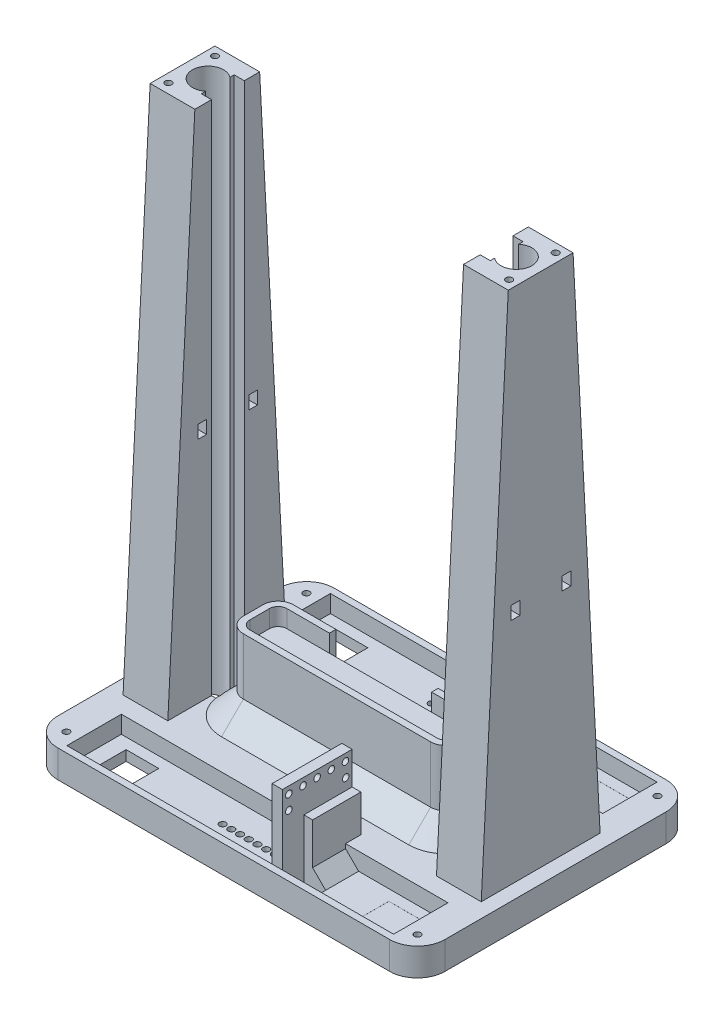
SolidWorks part; units mm, degrees
ref_plane "Front Plane" through (0, 0, 0) normal (0, 0, 1) x (1, 0, 0)
ref_plane "Top Plane" through (0, 0, 0) normal (0, 1, 0) x (1, 0, 0)
ref_plane "Right Plane" through (0, 0, 0) normal (1, 0, 0) x (0, 0, -1)
sketch "Sketch1" plane through (0, 0, 0) normal (0, 1, 0) x (1, 0, 0)
  line L1 (-76.2, 63.5) -> (76.2, 63.5)
  line L2 (-88.9, 50.8) -> (-88.9, -50.8)
  line L3 (-76.2, -63.5) -> (76.2, -63.5)
  line L4 (88.9, 50.8) -> (88.9, -50.8)
  line L5 (-88.9, 63.5) -> (88.9, -63.5) construction
  line L6 (-88.9, -63.5) -> (88.9, 63.5) construction
  arc A0 (-88.9, -50.8) -> (-76.2, -63.5) centre (-76.2, -50.8) ccw
  arc A1 (76.2, -63.5) -> (88.9, -50.8) centre (76.2, -50.8) ccw
  arc A2 (76.2, 63.5) -> (88.9, 50.8) centre (76.2, 50.8) cw
  arc A3 (-76.2, 63.5) -> (-88.9, 50.8) centre (-76.2, 50.8) ccw
  point P0 (0, 0)
  dimension "D3" = 12.7
  dimension "D1" = 177.8
  dimension "D2" = 127
extrude "Boss-Extrude1" add sketch "Sketch1" along normal blind 12.7
sketch "Sketch4" plane through (0, 12.7, 0) normal (0, 1, 0) x (1, 0, 0)
  line L5 (45, -6.5) -> (-45, -6.5)
  line L6 (45, -6.5) -> (45, 6.5)
  line L7 (45, 6.5) -> (-45, 6.5)
  line L8 (-45, -6.5) -> (-45, 6.5)
  line L9 (45, -6.5) -> (-45, 6.5) construction
  line L10 (45, 6.5) -> (-45, -6.5) construction
  point P0 (0, 0)
  dimension "D1" = 13
  dimension "D2" = 90
extrude "Cut-Extrude3" cut sketch "Sketch4" against normal blind 8
sketch "Sketch5" plane through (0, 12.7, 0) normal (0, 1, 0) x (1, 0, 0)
  line L0 (45, 6.5) -> (-45, 6.5) construction
  line L1 (-16.4675, 6.5) -> (-21.4675, 6.5)
  line L2 (-16.4675, 6.5) -> (-16.4675, 56.5)
  line L3 (-16.4675, 56.5) -> (-21.4675, 56.5)
  line L4 (-21.4675, 6.5) -> (-21.4675, 56.5)
  line L5 (0, -6.985) -> (0, 6.985) construction
  line L6 (16.4675, 56.5) -> (21.4675, 56.5)
  line L7 (21.4675, 6.5) -> (21.4675, 56.5)
  line L8 (16.4675, 6.5) -> (21.4675, 6.5)
  line L9 (16.4675, 6.5) -> (16.4675, 56.5)
  dimension "D1" = 5
  dimension "D2" = 50
  dimension "D3" = 16.4675
extrude "Cut-Extrude4" cut sketch "Sketch5" against normal up to surface (8 mm away) up to face at (0, 4.7, 0)
fillet "Fillet2" radius 2 36 edges at (21.4675, 4.7, -31.5) (21.4675, 12.7, -31.5) (16.4675, 4.7, -31.5) (16.4675, 12.7, -31.5) (-16.4675, 4.7, -31.5) (-16.4675, 12.7, -31.5) (-21.4675, 4.7, -31.5) (-21.4675, 12.7, -31.5) (-45, 4.7, 0) (-45, 12.7, 0) (-45, 8.7, 6.5) (0, 4.7, 6.5) (0, 12.7, 6.5) (45, 8.7, 6.5) (45, 4.7, 0) (45, 12.7, 0) (45, 8.7, -6.5) (33.2338, 4.7, -6.5) (21.4675, 8.7, -6.5) (33.2338, 12.7, -6.5) (16.4675, 8.7, -6.5) (0, 4.7, -6.5) (-16.4675, 8.7, -6.5) (0, 12.7, -6.5) (-45, 8.7, -6.5) (-33.2338, 12.7, -6.5) (-21.4675, 8.7, -6.5) (-33.2338, 4.7, -6.5) (-21.4675, 8.7, -56.5) (-18.9675, 12.7, -56.5) (-16.4675, 8.7, -56.5) (-18.9675, 4.7, -56.5) (16.4675, 8.7, -56.5) (18.9675, 12.7, -56.5) (21.4675, 8.7, -56.5) (18.9675, 4.7, -56.5)
sketch "Sketch8" plane through (0, 12.7, 0) normal (0, 1, 0) x (1, 0, 0)
  line L0 (-76.2, -63.5) -> (76.2, -63.5) construction
  line L1 (-75, -35.5) -> (75, -35.5)
  line L2 (-75, -35.5) -> (-75, -60.5)
  line L3 (-75, -60.5) -> (75, -60.5)
  line L4 (75, -35.5) -> (75, -60.5)
  line L5 (-6.985, 0) -> (6.985, 0) construction
  line L6 (-75, 60.5) -> (75, 60.5)
  line L7 (75, 35.5) -> (75, 60.5)
  line L8 (-75, 35.5) -> (75, 35.5)
  line L9 (-75, 35.5) -> (-75, 60.5)
  point P4 (0, -60.5)
  dimension "D1" = 25
  dimension "D2" = 150
  dimension "D3" = 3
extrude "Cut-Extrude7" cut sketch "Sketch8" against normal blind 8
sketch "Sketch9" plane through (0, 4.7, 0) normal (0, 1, 0) x (1, 0, 0)
  line L0 (-75, -35.5) -> (-75, -60.5) construction
  line L1 (0, -6.985) -> (0, 6.985) construction
  line L2 (-6.985, 0) -> (6.985, 0) construction
  circle A0 centre (0, -48) radius 1.5
  circle A1 centre (4, -48) radius 1.5
  circle A2 centre (8, -48) radius 1.5
  circle A3 centre (12, -48) radius 1.5
  circle A4 centre (16, -48) radius 1.5
  circle A5 centre (-16, -48) radius 1.5
  circle A6 centre (-12, -48) radius 1.5
  circle A7 centre (-8, -48) radius 1.5
  circle A8 centre (-4, -48) radius 1.5
  circle A9 centre (-4, 48) radius 1.5
  circle A10 centre (-8, 48) radius 1.5
  circle A11 centre (-12, 48) radius 1.5
  circle A12 centre (-16, 48) radius 1.5
  circle A13 centre (16, 48) radius 1.5
  circle A14 centre (12, 48) radius 1.5
  circle A15 centre (8, 48) radius 1.5
  circle A16 centre (4, 48) radius 1.5
  circle A17 centre (0, 48) radius 1.5
  point P7 (-75, -48)
  dimension "D1" = 3
  dimension "D2" = 5
extrude "Cut-Extrude8" cut sketch "Sketch9" against normal blind 8
sketch "Sketch10" plane through (0, 4.7, 0) normal (0, 1, 0) x (1, 0, 0)
  line L0 (-75, -35.5) -> (-75, -60.5) construction
  line L1 (-67.8176, -40.5) -> (-52.8176, -40.5)
  line L2 (-67.8176, -40.5) -> (-67.8176, -55.5)
  line L3 (-67.8176, -55.5) -> (-52.8176, -55.5)
  line L4 (-52.8176, -40.5) -> (-52.8176, -55.5)
  line L5 (0, -6.985) -> (0, 6.985) construction
  line L6 (52.8176, -40.5) -> (52.8176, -55.5)
  line L7 (67.8176, -40.5) -> (52.8176, -40.5)
  line L8 (67.8176, -55.5) -> (52.8176, -55.5)
  line L9 (67.8176, -40.5) -> (67.8176, -55.5)
  line L10 (-6.985, 0) -> (6.985, 0) construction
  line L11 (-75, 35.5) -> (-75, 60.5) construction
  line L12 (67.8176, 40.5) -> (67.8176, 55.5)
  line L13 (67.8176, 55.5) -> (52.8176, 55.5)
  line L14 (67.8176, 40.5) -> (52.8176, 40.5)
  line L15 (52.8176, 40.5) -> (52.8176, 55.5)
  line L16 (-52.8176, 40.5) -> (-52.8176, 55.5)
  line L17 (-67.8176, 55.5) -> (-52.8176, 55.5)
  line L18 (-67.8176, 40.5) -> (-67.8176, 55.5)
  line L19 (-67.8176, 40.5) -> (-52.8176, 40.5)
  point P8 (-67.8176, -48)
  point P9 (-75, -48)
  dimension "D1" = 15
extrude "Cut-Extrude9" cut sketch "Sketch10" against normal blind 8
sketch "Sketch11" plane through (0, 4.7, 0) normal (0, 1, 0) x (1, 0, 0)
  circle A0 centre (-19.4973, 37.2145) radius 2
  circle A1 centre (18.951, 37.4322) radius 2
  dimension "D1" = 4
  dimension "D2" = 4
extrude "Cut-Extrude10" cut sketch "Sketch11" against normal through all both and the other way through all
sketch "Sketch13" plane through (0, 12.7, 0) normal (0, 1, 0) x (1, 0, 0)
  line L1 (-82.2291, 27.1098) -> (-57.5332, 27.1098)
  line L2 (-82.2291, 27.1098) -> (-82.2291, -27.4812)
  line L3 (-82.2291, -27.4812) -> (-57.5332, -27.4812)
  line L4 (-57.5332, 27.1098) -> (-57.5332, -27.4812)
extrude "Boss-Extrude2" add sketch "Sketch13" along normal blind 242
sketch "Sketch14" plane through (-88.9, 0, 0) normal (-1, 0, 0) x (0, 0, 1)
  line L0 (-50.8, 12.7) -> (-50.8, 0)
  line L1 (-63.5, 0) -> (-50.8, 0) construction
  dimension "D1" = 12.7
sketch "Sketch17" plane through (-82.2291, 0, 0) normal (-1, 0, 0) x (0, 0, 1)
  line L0 (-27.1098, 12.7) -> (-14.6891, 249.7)
  line L1 (-27.1098, 254.7) -> (27.4812, 254.7) construction
  line L2 (-14.4271, 254.7) -> (14.7985, 254.7)
  line L3 (15.0605, 249.7) -> (27.4812, 12.7)
  line L4 (-50.8, 12.7) -> (50.8, 12.7) construction
  line L5 (27.4812, 254.7) -> (27.4812, 12.7) construction
  line L6 (27.4812, 12.7) -> (27.4812, 254.7)
  line L7 (27.4812, 254.7) -> (-27.1098, 254.7)
  line L8 (-27.1098, 254.7) -> (-27.1098, 12.7)
  line L9 (-14.6891, 249.7) -> (15.0605, 249.7)
  line L10 (27.4812, 249.7) -> (27.4812, 254.7)
  line L11 (-27.1098, 254.7) -> (-27.1098, 249.7)
  line L12 (-27.1098, 254.7) -> (27.4812, 254.7)
  line L13 (-27.1098, 12.7) -> (27.4812, 12.7) construction
  line L15 (-27.1098, 254.7) -> (27.4812, 254.7)
  line L16 (-27.1098, 254.7) -> (-27.1098, 249.7)
  line L17 (-14.6891, 249.7) -> (15.0605, 249.7)
  line L18 (27.4812, 254.7) -> (27.4812, 249.7)
  line M6 (27.4812, 12.7) -> (27.4812, 254.7)
  line M7 (27.4812, 254.7) -> (-27.1098, 254.7)
  line M8 (-27.1098, 254.7) -> (-27.1098, 12.7)
  dimension "D1" = 93
  dimension "D2" = 93
  dimension "D3" = 237
extrude "Cut-Extrude11" cut sketch "Sketch17" against normal through all both and the other way through all contours L0 M8 M7 | L3 M7 M6
mirror "Mirror1" about plane through (0, 0, 0) normal (1, 0, 0) of "Cut-Extrude11", "Boss-Extrude2"
sketch "Sketch19" plane through (0, 249.7, 0) normal (0, 1, 0) x (1, 0, 0)
  line L0 (-57.5332, 14.6891) -> (57.5332, 14.6891) construction
  dimension "D1" = 115.0664
sketch "Sketch21" plane through (57.5332, 0, 0) normal (-1, 0, 0) x (0, 0, 1)
  line L0 (27.4812, 12.7) -> (-27.1098, 12.7) construction
  line L1 (9.7062, 123.7) -> (13.7062, 123.7)
  line L2 (9.7062, 123.7) -> (9.7062, 117.7)
  line L3 (9.7062, 117.7) -> (13.7062, 117.7)
  line L4 (13.7062, 123.7) -> (13.7062, 117.7)
  line L5 (7.0117, -156.1376) -> (10.8153, 75.1843) construction
  point P4 (11.7062, 117.7)
  dimension "D1" = 105
  dimension "D2" = 6
  dimension "D3" = 4
extrude "Cut-Extrude12" cut sketch "Sketch21" against normal through all both and the other way through all
mirror "Mirror2" about plane through (0, 0, 0) normal (0, 0, 1) of "Cut-Extrude12"
sketch "Sketch24" plane through (-57.5332, 0, 0) normal (1, 0, 0) x (0, 0, -1)
  line L0 (-9.7062, 117.7) -> (-9.7062, 249.7) construction
  line L1 (14.6891, 249.7) -> (-15.0605, 249.7) construction
  line L2 (9.7062, 117.7) -> (9.7062, 249.7) construction
sketch "Sketch25" plane through (0, 249.7, 0) normal (0, 1, 0) x (1, 0, 0)
  line L0 (-66.3346, -5.4197) -> (-66.3346, -7.4365)
  line L1 (-57.3174, 7.6489) -> (-66.3346, 7.6489)
  line L2 (-57.3174, 7.6489) -> (-57.3174, -7.4365)
  line L3 (-57.3174, -7.4365) -> (-66.3346, -7.4365)
  line L4 (-66.3346, 7.6489) -> (-66.3346, 5.6322)
  line L5 (0, -69.85) -> (0, 69.85) construction
  line L6 (66.3346, 7.6489) -> (66.3346, 5.6322)
  line L7 (57.3174, -7.4365) -> (66.3346, -7.4365)
  line L8 (57.3174, 7.6489) -> (57.3174, -7.4365)
  line L9 (57.3174, 7.6489) -> (66.3346, 7.6489)
  line L10 (66.3346, -5.4197) -> (66.3346, -7.4365)
  arc A1 (-66.3346, 5.6322) -> (-66.3346, -5.4197) centre (-70.8135, 0.1062) ccw
  arc A2 (66.3346, 5.6322) -> (66.3346, -5.4197) centre (70.8135, 0.1062) cw
extrude "Cut-Extrude13" cut sketch "Sketch25" against normal through all both and the other way through all
sketch "Sketch26" plane through (0, 249.7, 0) normal (0, 1, 0) x (1, 0, 0)
  line L0 (-57.5332, 14.6891) -> (-82.2291, 14.6891) construction
  line L1 (-82.2291, -15.0605) -> (-82.2291, 14.6891) construction
  line L2 (-97.79, 0) -> (97.79, 0) construction
  line L3 (0, -69.85) -> (0, 69.85) construction
  circle A0 centre (-78.2291, 10.6891) radius 1.5
  circle A1 centre (-78.2291, -10.6891) radius 1.5
  circle A2 centre (78.2291, -10.6891) radius 1.5
  circle A3 centre (78.2291, 10.6891) radius 1.5
  dimension "D1" = 3
  dimension "D2" = 4
  dimension "D3" = 4
extrude "Cut-Extrude14" cut sketch "Sketch26" against normal blind 9 and the other way through all
sketch "Sketch27" plane through (0, 4.7, 0) normal (0, 1, 0) x (1, 0, 0)
  line L0 (0, 48) -> (0, -48) construction
  line L1 (76.2, 63.5) -> (-76.2, 63.5) construction
  line L2 (-88.9, 50.8) -> (-88.9, -50.8) construction
  circle A0 centre (-78.2291, 10.6891) radius 1.5 construction
  circle A1 centre (-78.2291, 10.6891) radius 1.5 construction
  circle A2 centre (-78.2291, -10.6891) radius 1.5 construction
  dimension "D1" = 96
  dimension "D2" = 15.5
sketch "Sketch28" plane through (0, 249.7, 0) normal (0, 1, 0) x (1, 0, 0)
  line L0 (-75, 35.5) -> (-20.527, 35.5) construction
  line L1 (-61.6873, 35.5) -> (-50.4908, 35.5)
  line L2 (-61.6873, 35.5) -> (-61.6873, -35.5)
  line L3 (-61.6873, -35.5) -> (-50.4908, -35.5)
  line L4 (-50.4908, 35.5) -> (-50.4908, -35.5)
  line L5 (75, -35.5) -> (-75, -35.5) construction
extrude "Cut-Extrude15" cut sketch "Sketch28" against normal up to surface and the other way through all
mirror "Mirror3" about plane through (0, 0, 0) normal (1, 0, 0) of "Cut-Extrude15"
sketch "Sketch29" plane through (0, 4.7, 0) normal (0, 1, 0) x (1, 0, 0)
  line L1 (19.2266, -28.4765) -> (23.9459, -28.4765)
  line L2 (19.2266, -28.4765) -> (19.2266, -60.4765)
  line L3 (19.2266, -60.4765) -> (23.9459, -60.4765)
  line L4 (23.9459, -28.4765) -> (23.9459, -60.4765)
  dimension "D1" = 32
extrude "Boss-Extrude3" add sketch "Sketch29" along normal blind 40
chamfer "Chamfer1" distance 10 angle 45 1 edges at (23.9459, 4.7, 47.9883)
sketch "Sketch30" plane through (23.9459, 0, 0) normal (1, 0, 0) x (0, 0, -1)
  circle A0 centre (-44.5341, 41.4487) radius 1.5
  circle A1 centre (-51.0341, 41.4487) radius 1.5
  circle A2 centre (-57.5341, 41.4487) radius 1.5
  circle A3 centre (-57.5341, 34.9487) radius 1.5
  circle A4 centre (-38.0344, 41.3919) radius 1.5
  circle A5 centre (-31.5344, 41.3849) radius 1.5
  dimension "D2" = 3
  dimension "D3" = 3
  dimension "D4" = 3
  dimension "D5" = 3
  dimension "D8" = 3
  dimension "D9" = 3
  dimension "D1" = 6.5
  dimension "D6" = 6.5
  dimension "D7" = 6.5
  dimension "D10" = 6.5
  dimension "D11" = 6.5
sketch "Sketch31" plane through (23.9459, 0, 0) normal (1, 0, 0) x (0, 0, -1)
  line L0 (-60.4765, 44.7) -> (-60.4765, 14.7) construction
  line L1 (-60.4765, 29.7) -> (-28.4765, 29.7)
  line L2 (-60.4765, 29.7) -> (-60.4765, 1.9326)
  line L3 (-60.4765, 1.9326) -> (-28.4765, 1.9326)
  line L4 (-28.4765, 29.7) -> (-28.4765, 1.9326)
  line L5 (-28.4765, 44.7) -> (-28.4765, 14.7) construction
  line L6 (-60.4765, 44.7) -> (-28.4765, 44.7) construction
  dimension "D1" = 15
extrude "Boss-Extrude4" add sketch "Sketch31" along normal blind 4
sketch "Sketch32" plane through (23.9459, 0, 0) normal (1, 0, 0) x (0, 0, -1)
extrude "Cut-Extrude16" cut sketch "Sketch30" against normal blind 6
sketch "Sketch34" plane through (0, 29.7, 0) normal (0, 1, 0) x (1, 0, 0)
  line L0 (23.9459, -28.4765) -> (23.9459, -60.4765) construction
  line L1 (23.9459, -50.6327) -> (30.9459, -50.6327)
  line L2 (23.9459, -50.6327) -> (23.9459, -60.4765)
  line L3 (23.9459, -60.4765) -> (30.9459, -60.4765)
  line L5 (33.9459, -60.4765) -> (27.9459, -60.4765) construction
  line L6 (30.9459, -50.6327) -> (33.9459, -50.6327)
  line L7 (33.9459, -35.5) -> (33.9459, -60.4765) construction
  line L8 (33.9459, -50.6327) -> (33.9459, -60.4765)
  line L9 (33.9459, -60.4765) -> (30.9459, -60.4765)
extrude "Cut-Extrude17" cut sketch "Sketch34" against normal through all
mirror "Mirror9" about plane through (0, 0, 0) normal (0, 0, 1) of "Cut-Extrude17", "Boss-Extrude3", "Boss-Extrude4", "Cut-Extrude16"
fillet "Fillet3" radius 10 1 edges at (27.9459, 4.7, -43.0663)
sketch "Sketch36" plane through (67.8176, 0, 0) normal (-1, 0, 0) x (0, 0, 1)
  line L0 (-50.8, 0) -> (50.8, 0) construction
  line L1 (-37.9134, 0) -> (-63.2585, 0)
  line L2 (-37.9134, 0) -> (-37.9134, 4.6761)
  line L3 (-37.9134, 4.6761) -> (-63.2585, 4.6761)
  line L4 (-63.2585, 0) -> (-63.2585, 4.6761)
extrude "Boss-Extrude5" add sketch "Sketch36" along normal blind 21
mirror "Mirror10" about plane through (0, 0, 0) normal (0, 0, 1) of "Boss-Extrude5"
sketch "Sketch37" plane through (0, 12.7, 0) normal (0, 1, 0) x (1, 0, 0)
  line L54 (23.4675, 8.5) -> (43, 8.5) construction
  line L55 (47, 4.5) -> (47, -4.5) construction
  line L56 (43, -8.5) -> (-43, -8.5) construction
  line L57 (-47, -4.5) -> (-47, 4.5) construction
  line L58 (-43, 8.5) -> (-23.4675, 8.5) construction
  line L59 (23.4675, 11.5) -> (43, 11.5)
  line L60 (50, 4.5) -> (50, -4.5)
  line L61 (43, -11.5) -> (-43, -11.5)
  line L62 (-50, -4.5) -> (-50, 4.5)
  line L63 (-43, 11.5) -> (-23.4675, 11.5)
  line L64 (23.4675, 11.5) -> (43, 11.5)
  line L65 (50, 4.5) -> (50, -4.5)
  line L66 (43, -11.5) -> (-43, -11.5)
  line L67 (-50, -4.5) -> (-50, 4.5)
  line L68 (-43, 11.5) -> (-23.4675, 11.5)
  line L69 (23.4675, 8.5) -> (43, 8.5)
  line L70 (47, 4.5) -> (47, -4.5)
  line L71 (43, -8.5) -> (-43, -8.5)
  line L72 (-47, -4.5) -> (-47, 4.5)
  line L73 (-43, 8.5) -> (-23.4675, 8.5)
  line L74 (-23.4675, 11.5) -> (-23.4675, 8.5)
  line L75 (23.4675, 11.5) -> (23.4675, 8.5)
  arc A40 (47, 4.5) -> (43, 8.5) centre (43, 4.5) ccw construction
  arc A41 (43, -8.5) -> (47, -4.5) centre (43, -4.5) ccw construction
  arc A42 (-47, -4.5) -> (-43, -8.5) centre (-43, -4.5) ccw construction
  arc A43 (-43, 8.5) -> (-47, 4.5) centre (-43, 4.5) ccw construction
  arc A44 (50, 4.5) -> (43, 11.5) centre (43, 4.5) ccw
  arc A45 (43, -11.5) -> (50, -4.5) centre (43, -4.5) ccw
  arc A46 (-50, -4.5) -> (-43, -11.5) centre (-43, -4.5) ccw
  arc A47 (-43, 11.5) -> (-50, 4.5) centre (-43, 4.5) ccw
  arc A48 (50, 4.5) -> (43, 11.5) centre (43, 4.5) ccw
  arc A49 (43, -11.5) -> (50, -4.5) centre (43, -4.5) ccw
  arc A50 (-50, -4.5) -> (-43, -11.5) centre (-43, -4.5) ccw
  arc A51 (-43, 11.5) -> (-50, 4.5) centre (-43, 4.5) ccw
  arc A52 (47, 4.5) -> (43, 8.5) centre (43, 4.5) ccw
  arc A53 (43, -8.5) -> (47, -4.5) centre (43, -4.5) ccw
  arc A54 (-47, -4.5) -> (-43, -8.5) centre (-43, -4.5) ccw
  arc A55 (-43, 8.5) -> (-47, 4.5) centre (-43, 4.5) ccw
  dimension "D1" = 3
extrude "Boss-Extrude6" add sketch "Sketch37" along normal offset from surface (36 mm away) 4 up to face at (21.5863, 44.7, 44.4765) offset beyond the face yes
sketch "Sketch38" plane through (23.9459, 0, 0) normal (1, 0, 0) x (0, 0, -1)
  circle A0 centre (31.4285, 34.8849) radius 1.5
  circle A1 centre (31.5344, 41.3849) radius 1.5 construction
  dimension "D1" = 3
  dimension "D2" = 6.5
extrude "Cut-Extrude18" cut sketch "Sketch38" against normal through all
chamfer "Chamfer4" distance 10 angle 45 9 edges at (-33.2338, 12.7, -11.5) (33.2338, 12.7, -11.5) (-47.9497, 12.7, -9.4497) (47.9497, 12.7, -9.4497) (-50, 12.7, 0) (50, 12.7, 0) (-47.9497, 12.7, 9.4497) (47.9497, 12.7, 9.4497) (0, 12.7, 11.5)
sketch "Sketch39" plane through (0, 4.7, 0) normal (0, 1, 0) x (1, 0, 0)
  line L1 (-47, 8.5) -> (47.9497, 8.5)
  line L2 (-47, 8.5) -> (-47, -9.4497)
  line L3 (-47, -9.4497) -> (47.9497, -9.4497)
  line L4 (47.9497, 8.5) -> (47.9497, -9.4497)
  arc A0 (43, -11.5) -> (50, -4.5) centre (43, -4.5) ccw construction
extrude "Boss-Extrude7" add sketch "Sketch39" along normal offset from surface (36 mm away) 8 up to face at (0, 48.7, -2)
mirror "Mirror11" about plane through (0, 0, 0) normal (0, 0, 1) of "Cut-Extrude18"
sketch "Sketch40" plane through (0, 12.7, 0) normal (0, 1, 0) x (1, 0, 0)
  line L0 (0, -69.85) -> (0, 69.85) construction
  line L1 (-97.79, 0) -> (97.79, 0) construction
  circle A0 centre (-80.6217, 55.0886) radius 1.5
  circle A1 centre (80.6217, 55.0886) radius 1.5
  circle A2 centre (80.6217, -55.0886) radius 1.5
  circle A3 centre (-80.6217, -55.0886) radius 1.5
  point P2 (0, 0)
  point P4 (0, 0)
  point P5 (-90.0655, 49.3174)
  point P6 (-80.6217, 55.0886)
  dimension "D1" = 3
extrude "Cut-Extrude19" cut sketch "Sketch40" against normal through all
sketch "Sketch41" plane through (0, 12.7, 0) normal (0, 1, 0) x (1, 0, 0)
  line L0 (-85.1803, -59.7803) -> (-77.26, -51.6287) construction
  arc A1 (-88.9, -50.8) -> (-76.2, -63.5) centre (-76.2, -50.8) ccw construction
